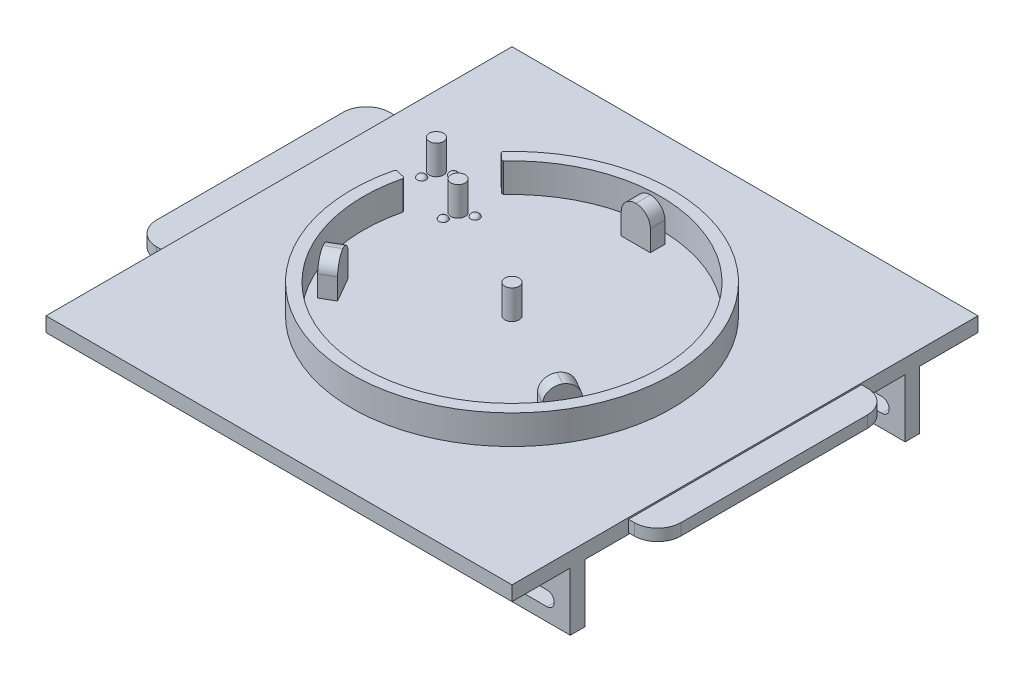
SolidWorks part; units mm, degrees
ref_plane "Vorne" through (0, 0, 0) normal (0, 0, 1) x (1, 0, 0)
ref_plane "Oben" through (0, 0, 0) normal (0, 1, 0) x (1, 0, 0)
ref_plane "Seite" through (0, 0, 0) normal (1, 0, 0) x (0, 0, -1)
sketch "Skizze1" plane through (0, 0, 0) normal (0, 1, 0) x (1, 0, 0)
  line L1 (80, -80) -> (-80, -80)
  line L2 (80, -80) -> (80, 80)
  line L3 (80, 80) -> (-80, 80)
  line L4 (-80, -80) -> (-80, 80)
  line L5 (80, -80) -> (-80, 80) construction
  line L6 (80, 80) -> (-80, -80) construction
  point P0 (0, 0)
  dimension "D1" = 160
extrude "Aufsatz-Linear austragen1" add sketch "Skizze1" along normal mid plane 5
sketch "Skizze2" plane through (0, -2.5, 0) normal (0, -1, 0) x (-1, 0, 0)
  line L0 (-80, 0) -> (80, 0) construction
  line L5 (80, -57.5) -> (-80, -57.5) construction
  line L6 (80, 55) -> (-80, 55)
  line L7 (80, 55) -> (80, 60)
  line L8 (80, 60) -> (-80, 60)
  line L9 (-80, 55) -> (-80, 60)
  line L10 (0, 60) -> (0, 55) construction
  line L15 (-80, -80) -> (-80, 80) construction
  line L16 (80, 80) -> (80, -80) construction
  line L17 (0, -80) -> (0, 80) construction
  line L18 (80, -80) -> (-80, -80) construction
  line L19 (-80, 80) -> (80, 80) construction
  line L20 (80, 57.5) -> (-80, 57.5) construction
  line L21 (0, -60) -> (0, -55) construction
  line L22 (-80, -55) -> (-80, -60)
  line L23 (80, -60) -> (-80, -60)
  line L24 (80, -55) -> (80, -60)
  line L25 (80, -55) -> (-80, -55)
  point P28 (0, -57.5)
  point P672 (0, 57.5)
  dimension "D1" = 160
  dimension "D2" = 5
  dimension "D3" = 60
extrude "Aufsatz-Linear austragen2" add sketch "Skizze2" along normal blind 20
sketch "Skizze3" plane through (0, 0, 0) normal (0, 0, 1) x (1, 0, 0)
  line L0 (25, -13) -> (72, -13)
  line L1 (25, -18) -> (72, -18)
  line L2 (80, -22.5) -> (-80, -22.5) construction
  line L3 (80, -22.5) -> (80, -2.5) construction
  line L4 (-80, -22.5) -> (-80, -2.5) construction
  line L5 (-3.7, -22.5) -> (3.7, -22.5)
  circle A0 centre (-72, -15.5) radius 2.5
  arc A1 (72, -18) -> (72, -13) centre (72, -15.5) ccw
  arc A2 (25, -13) -> (25, -18) centre (25, -15.5) ccw
  arc A3 (3.7, -22.5) -> (-3.7, -22.5) centre (0, -22.5) ccw
  dimension "D2" = 5
  dimension "D6" = 3.7
  dimension "D1" = 7
  dimension "D3" = 47
  dimension "D4" = 8
  dimension "D5" = 8
extrude "Schnitt-Linear austragen1" cut sketch "Skizze3" against normal through all both and the other way through all
sketch "Skizze4" plane through (0, 2.5, 0) normal (0, 1, 0) x (1, 0, 0)
  line L0 (-49.4361, 12.5326) -> (-53.3135, 13.5156)
  line L1 (-80, 80) -> (-80, -80) construction
  line L2 (-37.7606, 34.2803) -> (-40.7222, 36.9689)
  line L3 (-49.4361, 12.5326) -> (-40, 21.4746) construction
  line L4 (-40, 21.4746) -> (-37.7606, 34.2803) construction
  line L5 (0, 0) -> (-40, 21.4746) construction
  line L6 (-40, 21.4746) -> (-80, 42.9493) construction
  circle A0 centre (0, 0) radius 2.45
  circle A3 centre (-40, 21.4746) radius 2.45
  arc A4 (-53.3135, 13.5156) -> (-40.7222, 36.9689) centre (0, 0) ccw
  arc A5 (-49.4361, 12.5326) -> (-37.7606, 34.2803) centre (0, 0) ccw
  circle A6 centre (-56.0352, 30.0834) radius 2.45
  dimension "D1" = 4.9
  dimension "D4" = 18.2
  dimension "D6" = 13
  dimension "D3" = 40
  dimension "55" = 55
  dimension "D5" = 51
  dimension "D2" = 45.4
extrude "Aufsatz-Linear austragen3" add sketch "Skizze4" along normal blind 10
chamfer "Fase1" distance 0.4 angle 45 4 edges at (-49.4361, 7.5, -12.5326) (-53.3135, 7.5, -13.5156) (-40.7222, 7.5, -36.9689) (-37.7606, 7.5, -34.2803)
sketch "Skizze6" plane through (0, 2.5, 0) normal (0, 1, 0) x (1, 0, 0)
  line L0 (0, 45) -> (-38.9711, -22.5) construction
  line L1 (-38.9711, -22.5) -> (38.9711, -22.5) construction
  line L2 (38.9711, -22.5) -> (0, 45) construction
  line L3 (0, 0) -> (-38.9711, -22.5) construction
  line L4 (0, 0) -> (38.9711, -22.5) construction
  line L5 (0, 0) -> (0, 45) construction
  line L6 (43.6362, -19.4199) -> (39.3061, -16.9199)
  line L7 (39.3061, -16.9199) -> (34.3061, -25.5801)
  line L8 (34.3061, -25.5801) -> (38.6362, -28.0801)
  line L9 (38.6362, -28.0801) -> (43.6362, -19.4199)
  line L10 (-34.3061, -25.5801) -> (-39.3061, -16.9199)
  line L11 (-39.3061, -16.9199) -> (-43.6362, -19.4199)
  line L12 (-43.6362, -19.4199) -> (-38.6362, -28.0801)
  line L13 (-38.6362, -28.0801) -> (-34.3061, -25.5801)
  line L14 (5, 42.5) -> (-5, 42.5)
  line L15 (-5, 42.5) -> (-5, 47.5)
  line L16 (-5, 47.5) -> (5, 47.5)
  line L17 (5, 47.5) -> (5, 42.5)
  line L18 (5, 47.5) -> (-5, 42.5) construction
  line L19 (-5, 47.5) -> (5, 42.5) construction
  line L20 (39.3061, -16.9199) -> (38.6362, -28.0801) construction
  line L21 (34.3061, -25.5801) -> (43.6362, -19.4199) construction
  line L22 (-38.6362, -28.0801) -> (-39.3061, -16.9199) construction
  line L23 (-43.6362, -19.4199) -> (-34.3061, -25.5801) construction
  circle A0 centre (0, 0) radius 45 construction
  point P3 (-38.9711, -22.5)
  point P4 (0, 45)
  point P5 (38.9711, -22.5)
  point P19 (0, 45)
  point P22 (38.9711, -22.5)
  point P23 (-38.9711, -22.5)
  dimension "D1" = 90
  dimension "D2" = 10
  dimension "D3" = 5
extrude "Aufsatz-Linear austragen4" add sketch "Skizze6" along normal blind 12.2 separate body
fillet "Verrundung1" radius 5 2 edges at (36.4711, 14.7, 26.8301) (41.4711, 14.7, 18.1699)
fillet "Verrundung2" radius 5 2 edges at (-36.4711, 14.7, 26.8301) (-41.4711, 14.7, 18.1699)
fillet "Verrundung3" radius 5 2 edges at (-5, 14.7, -45) (5, 14.7, -45)
sketch "Skizze7" plane through (0, 0, 0) normal (0, 1, 0) x (1, 0, 0)
  line L0 (-80, 40) -> (-90, 40)
  line L1 (-80, 80) -> (-80, -80) construction
  line L2 (-90, 40) -> (-90, -40)
  line L3 (-90, -40) -> (-80, -40)
  line L4 (80, 80) -> (-80, 80) construction
  line L5 (-80, 40) -> (-80, -40)
  line L6 (0, -50) -> (0, 50) construction
  line L7 (80, 40) -> (80, -40)
  line L8 (90, -40) -> (80, -40)
  line L9 (90, 40) -> (90, -40)
  line L10 (80, 40) -> (90, 40)
  dimension "D1" = 80
  dimension "D2" = 10
  dimension "D3" = 40
extrude "Aufsatz-Linear austragen5" add sketch "Skizze7" along normal mid plane 4
fillet "Verrundung4" radius 8 4 edges at (90, 0, 40) (90, 0, -40) (-90, 0, -40) (-90, 0, 40)
sketch "Skizze8" plane through (0, 2.5, 0) normal (0, 1, 0) x (1, 0, 0)
  line L0 (-51.8721, 31.7917) -> (-56.6374, 25.6239) construction
  line L1 (-56.6374, 25.6239) -> (-59.5962, 32.8347) construction
  line L2 (-59.5962, 32.8347) -> (-51.8721, 31.7917) construction
  line L3 (-43.561, 24.2259) -> (-40.6022, 17.0151) construction
  line L4 (-40.6022, 17.0151) -> (-35.8369, 23.1829) construction
  line L5 (-35.8369, 23.1829) -> (-43.561, 24.2259) construction
  circle A0 centre (-40, 21.4746) radius 4.5 construction
  circle A1 centre (-56.0352, 30.0834) radius 4.5 construction
  circle A2 centre (-59.5962, 32.8347) radius 1.5
  circle A3 centre (-56.6374, 25.6239) radius 1.5
  circle A4 centre (-51.8721, 31.7917) radius 1.5
  circle A5 centre (-43.561, 24.2259) radius 1.5
  circle A6 centre (-40.6022, 17.0151) radius 1.5
  circle A7 centre (-35.8369, 23.1829) radius 1.5
  dimension "D2" = 12
  dimension "D1" = 9
  dimension "D3" = 3
extrude "Aufsatz-Linear austragen6" add sketch "Skizze8" along normal mid plane 2
fillet "Verrundung5" radius 1.5 6 edges at (-40.6022, 3.5, -15.5151) (-35.8369, 3.5, -21.6829) (-51.8721, 3.5, -30.2917) (-43.561, 3.5, -22.7259) (-56.6374, 3.5, -24.1239) (-59.5962, 3.5, -31.3347)
